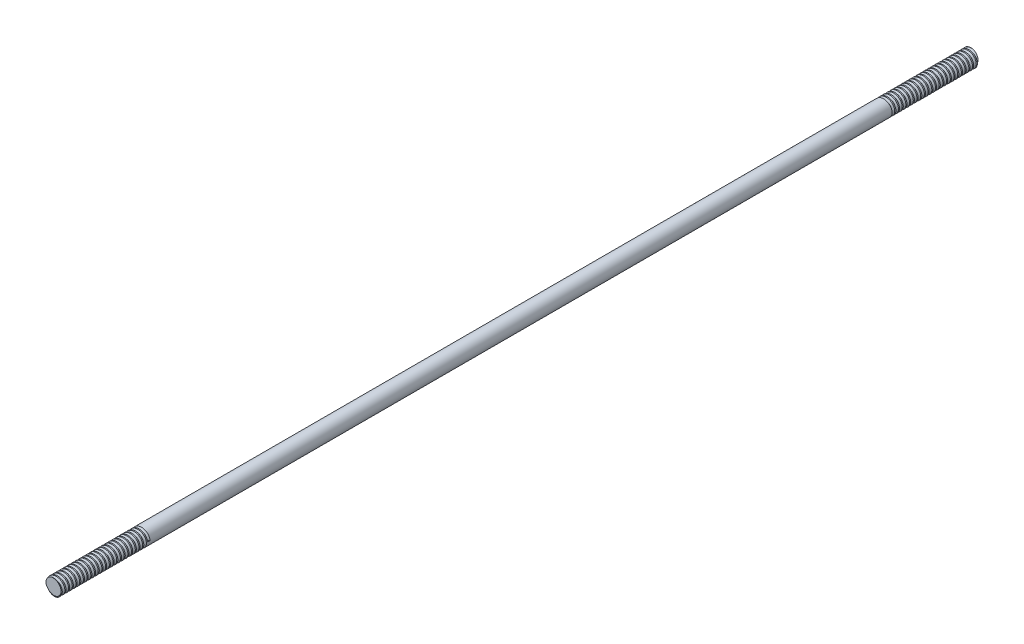
SolidWorks part; units mm, degrees
material "6061 Alloy"
ref_plane "Front Plane" through (0, 0, 0) normal (0, 0, 1) x (1, 0, 0)
ref_plane "Top Plane" through (0, 0, 0) normal (0, 1, 0) x (1, 0, 0)
ref_plane "Right Plane" through (0, 0, 0) normal (1, 0, 0) x (0, 0, -1)
sketch "Sketch1" plane through (0, 0, 0) normal (0, 0, 1) x (1, 0, 0)
  circle A0 centre (0, 0) radius 1.7526
  dimension "D1" = 3.5052
extrude "Rod" add sketch "Sketch1" along normal blind 196.6735
sketch "Sketch2" plane through (0, 0, 0) normal (0, 0, -1) x (-1, 0, 0)
  circle A0 centre (0, 0) radius 1.7526 construction
  circle A1 centre (0, 0) radius 1.7526
curve "Helix/Spiral1" pitch 0.7937 height 19.05 turns 24
sketch "Sketch4" plane through (0, 0, 0) normal (0, 1, 0) x (1, 0, 0)
  line L0 (-1.7526, 0) -> (1.7526, 0) construction
  line L1 (-1.7526, 0) -> (-1.7526, 0.5556)
  line L2 (-1.7526, 0.5556) -> (-1.3402, 0.3175)
  line L3 (-1.3402, 0.3175) -> (-1.3402, 0.2381)
  line L4 (-1.3402, 0.2381) -> (-1.7526, 0)
  line L5 (-1.3402, 0.2778) -> (-1.7526, 0.2778) construction
  line L6 (-1.5464, 0.4366) -> (-1.5464, 0.1191) construction
  dimension "D1" = 0.3175
  dimension "D2" = 0.0794
  dimension "D3" = 60
sweep "Thread 1" cut profiles "Sketch4" path "Helix/Spiral1"
sketch "Sketch6" plane through (0, 0, 0) normal (0, 1, 0) x (1, 0, 0)
  line L0 (1.7526, -196.6735) -> (1.7526, -197.2291)
  line L1 (1.7526, -197.2291) -> (1.3402, -196.991)
  line L2 (1.3402, -196.991) -> (1.3402, -196.9116)
  line L3 (1.3402, -196.9116) -> (1.7526, -196.6735)
  line L4 (1.3402, -196.9513) -> (1.7526, -196.9513) construction
  line L5 (1.5464, -197.11) -> (1.5464, -196.7925) construction
  line L7 (-1.7526, -196.6735) -> (1.7526, -196.6735) construction
  line L9 (-1.7526, -196.6735) -> (1.7526, -196.6735) construction
  dimension "D1" = 0.0794
  dimension "D2" = 0.3175
  dimension "D3" = 60
sketch "Sketch5" plane through (0, 0, 196.6735) normal (0, 0, 1) x (1, 0, 0)
  circle A1 centre (0, 0) radius 1.7526
  circle A2 centre (0, 0) radius 1.7526
  dimension "D1" = 0
curve "Helix/Spiral2" pitch 0.7937 height 19.05 turns 24
sweep "Thread 2" cut profiles "Sketch6" path "Helix/Spiral2"
